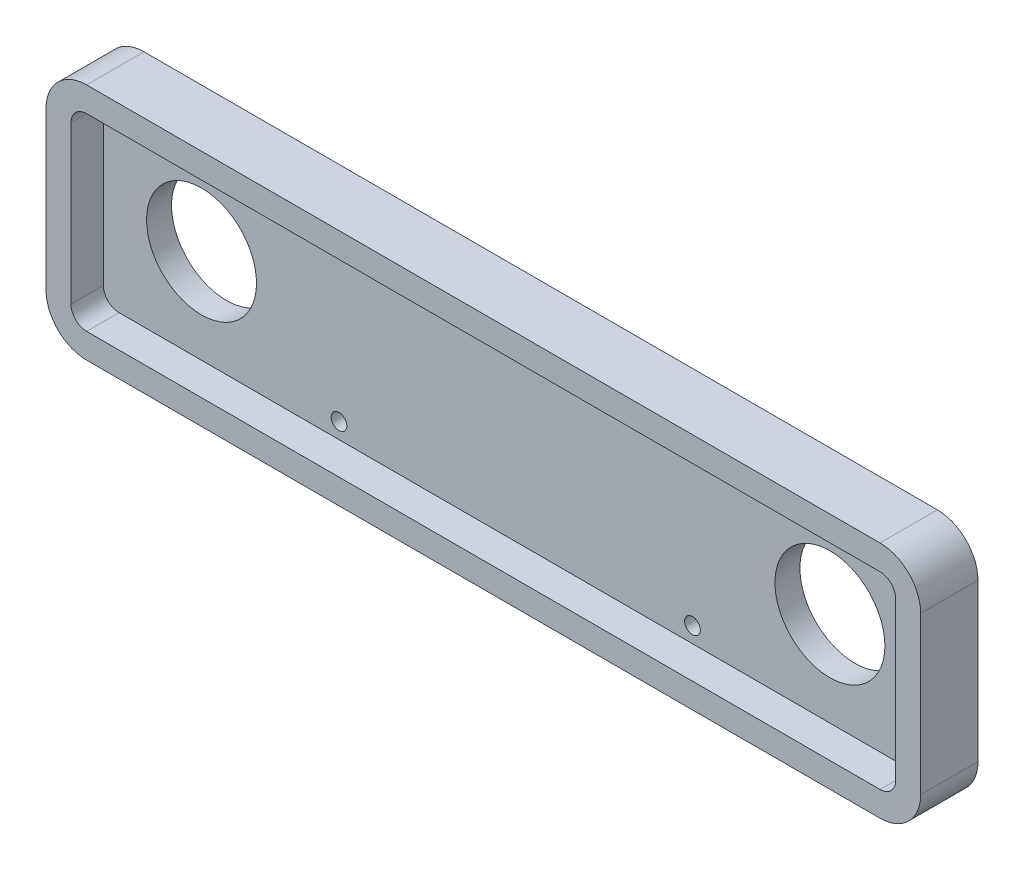
SolidWorks part; units mm, degrees
material "6061-T6 (SS)"
ref_plane "Front Plane" through (0, 0, 0) normal (0, 0, 1) x (1, 0, 0)
ref_plane "Top Plane" through (0, 0, 0) normal (0, 1, 0) x (1, 0, 0)
ref_plane "Right Plane" through (0, 0, 0) normal (1, 0, 0) x (0, 0, -1)
sketch "Sketch1" plane through (0, 0, 0) normal (0, 0, 1) x (1, 0, 0)
  line L0 (-50.5, 15.175) -> (50.5, 15.175)
  line L1 (-50.5, -12) -> (50.5, -12)
  line L2 (-52.5, -10) -> (-52.5, 10)
  line L3 (-50.5, 12) -> (50.5, 12)
  line L4 (52.5, -10) -> (52.5, 10)
  line L5 (-52.5, -12) -> (52.5, 12) construction
  line L6 (-52.5, 12) -> (52.5, -12) construction
  line L7 (55.675, -10) -> (55.675, 10)
  line L8 (-50.5, -15.175) -> (50.5, -15.175)
  line L9 (-55.675, -10) -> (-55.675, 10)
  arc A0 (-52.5, -10) -> (-50.5, -12) centre (-50.5, -10) ccw
  arc A1 (50.5, -12) -> (52.5, -10) centre (50.5, -10) ccw
  arc A2 (52.5, 10) -> (50.5, 12) centre (50.5, 10) ccw
  arc A3 (-50.5, 12) -> (-52.5, 10) centre (-50.5, 10) ccw
  arc A4 (55.675, 10) -> (50.5, 15.175) centre (50.5, 10) ccw
  arc A5 (50.5, -15.175) -> (55.675, -10) centre (50.5, -10) ccw
  arc A6 (-55.675, -10) -> (-50.5, -15.175) centre (-50.5, -10) ccw
  arc A7 (-50.5, 15.175) -> (-55.675, 10) centre (-50.5, 10) ccw
  point P0 (0, 0)
  dimension "D3" = 2
  dimension "D1" = 105
  dimension "D2" = 24
  dimension "D4" = 3.175
extrude "Boss-Extrude1" add sketch "Sketch1" along normal blind 7.3
extrude "Boss-Extrude2" add sketch "Sketch1<2>" along normal blind 3.175 contours L3 A3 L2 A0 L1 A1 L4 A2 region at (0, 0, 0)
sketch "Sketch1<2>" plane through (0, 0, 0) normal (0, 0, 1) x (1, 0, 0) same geometry as "Sketch1"
sketch "Sketch2" plane through (0, 0, 0) normal (0, 0, -1) x (-1, 0, 0)
  line L0 (-70.1691, 0) -> (70.1691, 0) construction
  line L1 (-22.5, -10) -> (22.5, -10) construction
  line L2 (-22.5, -10) -> (-22.5, 10) construction
  line L3 (-22.5, 10) -> (22.5, 10) construction
  line L4 (22.5, -10) -> (22.5, 10) construction
  line L5 (-22.5, -10) -> (22.5, 10) construction
  line L6 (-22.5, 10) -> (22.5, -10) construction
  line L7 (0, -26.7001) -> (0, 26.7001) construction
  circle A0 centre (22.5, 10) radius 1
  circle A1 centre (22.5, -10) radius 1
  circle A2 centre (-22.5, -10) radius 1
  circle A3 centre (-22.5, 10) radius 1
  point P0 (0, 0)
  point P10 (0, 0)
  point P13 (0, 0)
  dimension "D3" = 2
  dimension "D1" = 45
  dimension "D2" = 20
extrude "Cut-Extrude1" cut sketch "Sketch2" against normal up to surface (3.175 mm away) up to face at (0, 0, 3.175)
sketch "Sketch3" plane through (0, 0, 0) normal (0, 0, -1) x (-1, 0, 0)
  line L0 (-77.9557, 0) -> (77.9557, 0) construction
  line L1 (0, -31.8443) -> (0, 31.8443) construction
  circle A0 centre (40, 0) radius 7
  circle A1 centre (-40, 0) radius 7
  point P4 (0, 0)
  point P10 (0, 0)
  dimension "D1" = 14
  dimension "D2" = 40
extrude "Cut-Extrude2" cut sketch "Sketch3" against normal up to surface (3.175 mm away) up to face at (23.5, 10, 3.175)
hole_wizard "CSK for M2 Flat Head Machine Screw1" positions "3DSketch1" profile "Sketch4" countersink size "M2" standard "ANSI Metric"
sketch3d "3DSketch1"
  line L0 (22.5, 10, 3.175) -> (22.5, 10, 0) construction
  line L1 (-22.5, 10, 3.175) -> (-22.5, 10, 0) construction
  line L2 (-22.5, -10, 3.175) -> (-22.5, -10, 0) construction
  line L3 (22.5, -10, 3.175) -> (22.5, -10, 0) construction
  point P0 (22.5, 10, 0)
  point P4 (-22.5, 10, 0)
  point P8 (-22.5, -10, 0)
  point P12 (22.5, -10, 0)
sketch "Sketch4" plane through (22.5, 10, 0) normal (1, 0, 0) x (0, 1, 0)
  line L0 (0, 0) -> (0, 0.8109)
  line L1 (0, 0.8109) -> (1.1, 0.15)
  line L2 (1.1, 0.15) -> (1.1, 1.1)
  line L3 (1.1, 1.1) -> (2.2, 0)
  line L5 (2.2, 0) -> (0, 0)
  line L6 (-1.1, 1.1) -> (-2.2, 0) construction
  line L10 (0, 0.8109) -> (-1.1, 0.15) construction
  line L11 (0, -6.35) -> (0, 107.95) construction
  dimension "Hole Dia." = 2.2
  dimension "Hole Depth" = 0.15
  dimension "Near C'Sink Dia." = 4.4
  dimension "Near C'Sink Angle" = 90
  dimension "Drill Angle" = 118
